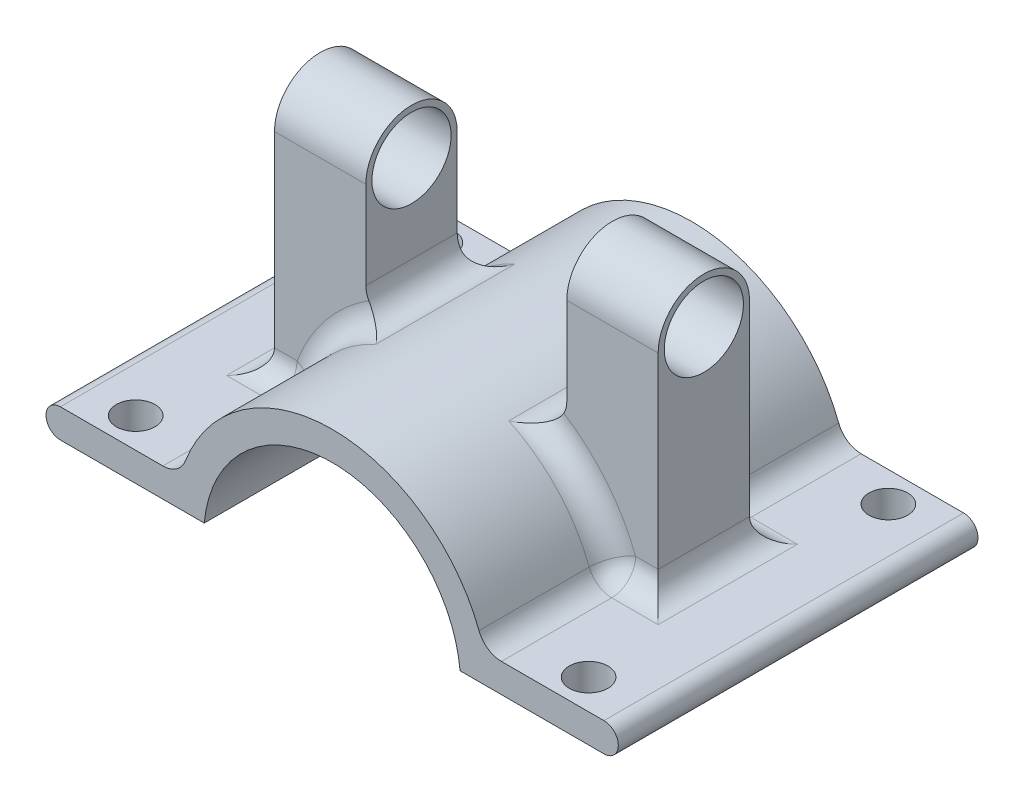
SolidWorks part; units mm, degrees
ref_plane "Front Plane" through (0, 0, 0) normal (0, 0, 1) x (1, 0, 0)
ref_plane "Top Plane" through (0, 0, 0) normal (0, 1, 0) x (1, 0, 0)
ref_plane "Right Plane" through (0, 0, 0) normal (1, 0, 0) x (0, 0, -1)
sketch "Sketch1" plane through (0, 0, 0) normal (0, 0, 1) x (1, 0, 0)
  line L0 (0, 0) -> (18.4493, 0) construction
  line L1 (10.6689, 1) -> (22.6673, 1)
  line L2 (22.6673, 3.4) -> (12.6673, 3.4)
  line L3 (0, 0) -> (0, 6.2202) construction
  line L7 (-10.6689, 1) -> (-22.6673, 1)
  line L8 (-22.6673, 3.4) -> (-12.6673, 3.4)
  arc A0 (10.6689, 1) -> (-10.6689, 1) centre (0, 0) ccw
  arc A1 (22.6673, 1) -> (22.6673, 3.4) centre (22.6673, 2.2) ccw
  arc A5 (-22.6673, 1) -> (-22.6673, 3.4) centre (-22.6673, 2.2) cw
  arc A6 (12.6673, 3.4) -> (0, 13.1156) centre (0, 0) ccw
  arc A7 (0, 13.1156) -> (-12.6673, 3.4) centre (0, 0) ccw
  point P14 (10.2474, 3.1329)
  point P27 (12.5425, 3.8346)
  dimension "D1" = 21.4312
  dimension "D4" = 1.2
  dimension "D8" = 13.1156
  dimension "D3" = 1
  dimension "D5" = 10
extrude "Boss-Extrude1" add sketch "Sketch1" along normal blind 30
sketch "Sketch3" plane through (0, 3.4, 0) normal (0, 1, 0) x (1, 0, 0)
  line L0 (22.6673, -30) -> (-22.6673, 0) construction
  line L1 (22.6673, 0) -> (-22.6673, -30) construction
  circle A0 centre (18.8894, -2.5) radius 1.6129
  circle A1 centre (-18.8894, -2.5) radius 1.6129
  circle A2 centre (-18.8894, -27.5) radius 1.6129
  circle A3 centre (18.8894, -27.5) radius 1.6129
  dimension "D1" = 3.2258
  dimension "D2" = 25
extrude "Cut-Extrude2" cut sketch "Sketch3" against normal through all
sketch "Sketch4" plane through (0, 3.4, 0) normal (0, 1, 0) x (1, 0, 0)
  line L0 (22.6673, -30) -> (22.6673, 0) construction
  line L1 (-8.38, -11.19) -> (-16, -11.19)
  line L2 (-8.38, -11.19) -> (-8.38, -18.81)
  line L3 (-8.38, -18.81) -> (-16, -18.81)
  line L4 (-16, -11.19) -> (-16, -18.81)
  line L5 (-8.38, -11.19) -> (-16, -18.81) construction
  line L6 (-8.38, -18.81) -> (-16, -11.19) construction
  line L7 (16, -11.19) -> (8.38, -11.19)
  line L8 (16, -11.19) -> (16, -18.81)
  line L9 (16, -18.81) -> (8.38, -18.81)
  line L10 (8.38, -11.19) -> (8.38, -18.81)
  line L11 (16, -11.19) -> (8.38, -18.81) construction
  line L12 (16, -18.81) -> (8.38, -11.19) construction
  line L13 (-22.6673, -30) -> (-22.6673, 0) construction
  line L14 (-22.6673, -15) -> (22.6673, -15) construction
  line L15 (0, 0) -> (0, -31.2057) construction
  point P0 (-12.19, -15)
  point P5 (12.19, -15)
  point P18 (0, -15)
  dimension "D1" = 7.62
  dimension "D2" = 32
extrude "Boss-Extrude2" add sketch "Sketch4" along normal blind 21.4312
sketch "Sketch5" plane through (-16, 0, 0) normal (-1, 0, 0) x (0, 0, 1)
  line L0 (15, 24.8313) -> (15, 21.0213) construction
  line L1 (11.19, 24.8313) -> (18.81, 24.8313) construction
  line L2 (11.19, 24.8313) -> (11.19, 3.4) construction
  line L3 (18.81, 24.8313) -> (18.81, 3.4) construction
  line L5 (18.81, 21.0213) -> (18.81, 24.8313)
  line L6 (18.81, 24.8313) -> (15, 24.8313)
  line L7 (11.19, 24.8313) -> (15, 24.8313)
  line L8 (11.19, 24.8313) -> (11.19, 21.0212)
  circle A0 centre (15, 21.0213) radius 3.302
  arc A1 (15, 24.8313) -> (11.19, 21.0212) centre (15, 21.0212) ccw
  arc A2 (15, 24.8313) -> (18.81, 21.0213) centre (15, 21.0213) cw
  dimension "D1" = 6.604
extrude "Cut-Extrude3" cut sketch "Sketch5" against normal up to surface (32 mm away)
sketch "Sketch6" plane through (0, 0, 30) normal (0, 0, 1) x (1, 0, 0)
  line L0 (-10.6689, 1) -> (10.6689, 1)
  arc A0 (10.6689, 1) -> (-10.6689, 1) centre (0, 0) ccw construction
  arc A1 (10.6689, 1) -> (-10.6689, 1) centre (0, 0) ccw
extrude "Cut-Extrude4" cut sketch "Sketch6" against normal through all
fillet "Fillet1" radius 2 16 edges at (12.6673, 3.4, 5.595) (12.6673, 3.4, 24.405) (8.38, 10.0894, 15) (11.0424, 7.0771, 11.19) (14.3336, 3.4, 11.19) (16, 3.4, 15) (14.3336, 3.4, 18.81) (11.0424, 7.0771, 18.81) (-8.38, 10.0894, 15) (-11.0424, 7.0771, 11.19) (-12.6673, 3.4, 5.595) (-14.3336, 3.4, 11.19) (-16, 3.4, 15) (-11.0424, 7.0771, 18.81) (-14.3336, 3.4, 18.81) (-12.6673, 3.4, 24.405)
fillet "Fillet2" [suppressed] radius 2
